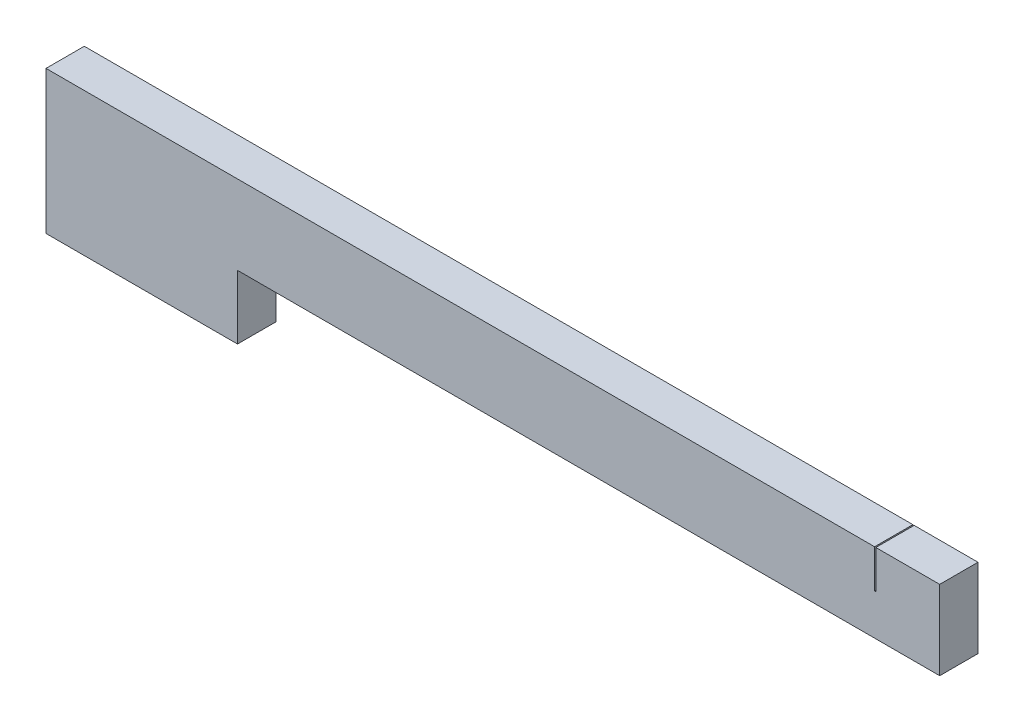
SolidWorks part; units mm, degrees
ref_plane "Front Plane" through (0, 0, 0) normal (0, 0, 1) x (1, 0, 0)
ref_plane "Top Plane" through (0, 0, 0) normal (0, 1, 0) x (1, 0, 0)
ref_plane "Right Plane" through (0, 0, 0) normal (1, 0, 0) x (0, 0, -1)
sketch "Sketch1" plane through (0, 0, 0) normal (0, 0, 1) x (1, 0, 0)
  line L0 (0, 0) -> (0, 11.2)
  line L1 (0, 11.2) -> (70, 11.2)
  line L2 (70, 11.2) -> (70, 5)
  line L3 (70, 5) -> (15, 5)
  line L4 (15, 5) -> (15, 0)
  line L5 (15, 0) -> (0, 0)
  dimension "D2" = 15
  dimension "D3" = 6.2
  dimension "D4" = 70
extrude "Boss-Extrude1" add sketch "Sketch1" along normal blind 3
sketch "Sketch3" plane through (0, 11.2, 0) normal (0, 1, 0) x (1, 0, 0)
  line L0 (0, -1.5) -> (64.95, -1.5) construction
  line L1 (0, -3) -> (0, 0) construction
  line L2 (70, 0) -> (0, 0) construction
  line L3 (64.9, -3) -> (65, -3)
  line L4 (64.9, -3) -> (64.9, 0)
  line L5 (64.9, 0) -> (65, 0)
  line L6 (65, -3) -> (65, 0)
  line L7 (64.9, -3) -> (65, 0) construction
  line L8 (64.9, 0) -> (65, -3) construction
  dimension "D1" = 64.95
extrude "Cut-Extrude1" cut sketch "Sketch3" against normal blind 3
equation "\"A.L\"= 0.06m"
equation "\"A.h\"= 0.005m"
equation "\"A.d\"= 0.003m"
equation "\"A.delta\"= 45.0001"
equation "\"A.w\"= 0.02m"
equation "\"A.v\"= 0.03m"
equation "\"A.s\"= 0.0075m"
equation "\"A.t\"= 0.005m"
equation "\"B.L\"= 0.04m"
equation "\"B.h\"= 0.004m"
equation "\"B.s\"= 0.008m"
equation "\"B.t\"= 0.004m"
equation "\"C.h\"= 0.0062m"
equation "\"C.d\"= 0.003m"
equation "\"C.L\"= 0.05m"
equation "\"C.wmax\"= 0.005m"
equation "\"D.L\"= 0.045m"
equation "\"D.h\"= 0.004m"
equation "\"D.s\"= 0.01m"
equation "\"D.t\"= 0.004m"
equation "\"a_h\"= 0.0001m"
equation "\"a_d\"= 0.003m"
equation "\"a_L\"= 0.01m"
equation "\"b_h\"= 0.0004m"
equation "\"b_d\"= 0.003m"
equation "\"b_L\"= 0.01m"
equation "\"c_h\"= 0.0001m"
equation "\"c_d\"= 0.003m"
equation "\"c_L\"= 0.01m"
equation "\"d_h\"= 0.0001m"
equation "\"d_d\"= 0.003m"
equation "\"d_L\"= 0.01m"
equation "\"S.h\"= 0.015m"
equation "\"S.L\"= 0.0559m"
equation "\"D1@Sketch1\"=\"C.h\"+\"C.wmax\""
equation "\"D2@Sketch1\"=\"S.h\""
equation "\"D3@Sketch1\"=\"C.h\""
equation "\"D4@Sketch1\"=\"C.L\"+\"S.h\"+0.005"
equation "\"D1@Boss-Extrude1\"=\"C.d\""
equation "\"D1@Sketch3\"=\"C.L\"+\"S.h\"-\"c_h\"/2"
equation "\"D2@Sketch3\"=\"c_h\""
